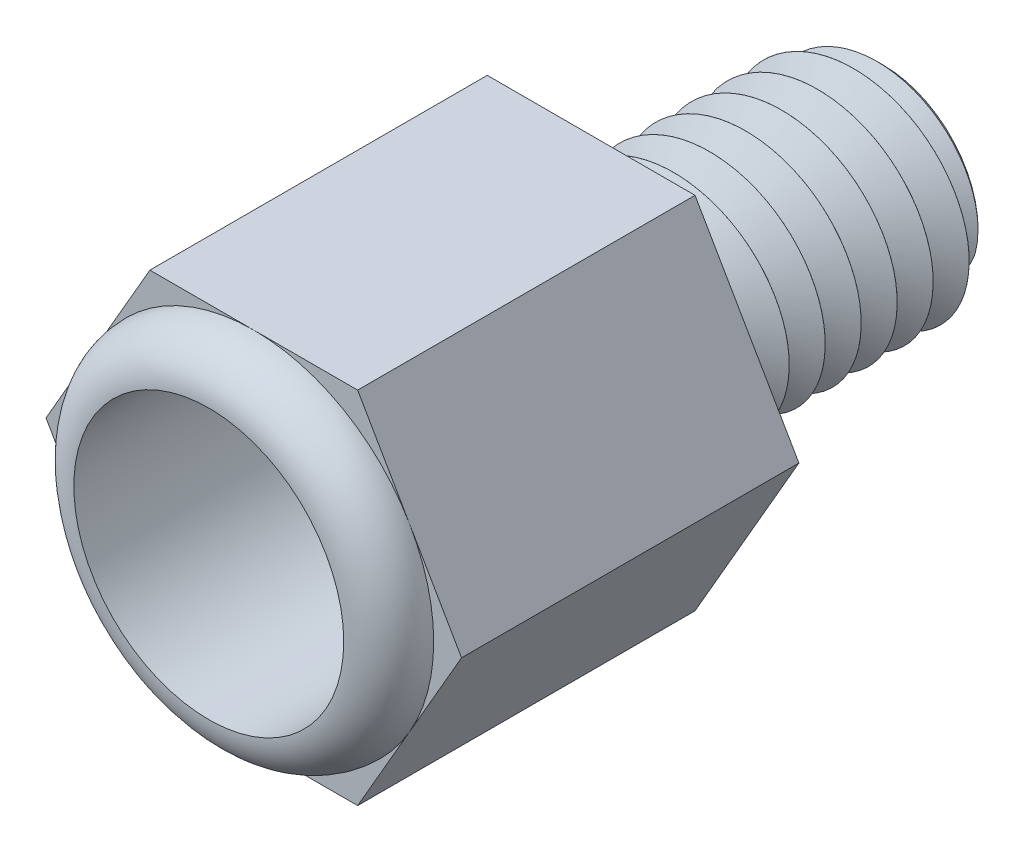
SolidWorks part; units mm, degrees
material "Bronze commercial, UNS C22000 (90-10 Bronze)"
ref_plane "Plan de face" through (0, 0, 0) normal (0, 0, 1) x (1, 0, 0)
ref_plane "Plan de dessus" through (0, 0, 0) normal (0, 1, 0) x (1, 0, 0)
ref_plane "Plan de droite" through (0, 0, 0) normal (1, 0, 0) x (0, 0, -1)
ref_plane "Plan1" through (0, 0, -0.8) normal (0, 0, 1) x (1, 0, 0)
sketch "Esquisse1" plane through (0, 0, 0) normal (0, 0, 1) x (1, 0, 0)
  line L1 (1.7321, 0) -> (0.866, 1.5)
  line L2 (0.866, 1.5) -> (-0.866, 1.5)
  line L3 (-0.866, 1.5) -> (-1.7321, 0)
  line L4 (-1.7321, 0) -> (-0.866, -1.5)
  line L5 (-0.866, -1.5) -> (0.866, -1.5)
  line L6 (0.866, -1.5) -> (1.7321, 0)
  circle A0 centre (0, 0) radius 2.5
  circle A1 centre (0, 0) radius 1.5 construction
  dimension "D1" = 5
  dimension "D2" = 3
extrude "Boss.-Extru.1" add sketch "Esquisse1" along normal blind 6.5
sketch "Forme" plane through (0, 0, 0) normal (1, 0, 0) x (0, 0, -1)
  line L0 (0, -1.808) -> (-0.3995, -2.5)
  line L1 (0, -2.5) -> (0, 2.5) construction
  line L2 (-0.3995, -2.5) -> (0.3995, -2.5)
  line L3 (0.3995, -2.5) -> (0, -1.808)
  line L4 (-6.5, -2.5) -> (0, -2.5) construction
  dimension "D1" = 60
  dimension "D2" = 0.799
sketch "Esquisse3" plane through (0, 0, -0.8) normal (0, 0, -1) x (-1, 0, 0)
  circle A0 centre (0, 0) radius 2.5
  dimension "D1" = 5
curve "Hélice/Spirale1" pitch 0.8 height 7 radius 2.5 centre (0, 0, -0.8) axis (0, 0, 1) start towards (-1, 0, 0)
chamfer "Chanfrein1" distance 0.4 angle 45 1 edges at (2.5, 0, 0)
sweep "Filetage M5" cut profiles "Forme" path "Hélice/Spirale1" align with end faces yes
sketch "Esquisse4" plane through (0, 0, 0) normal (0, 0, -1) x (-1, 0, 0)
  circle A0 centre (0, 0) radius 1.8
  dimension "D1" = 3.6
extrude "Enlèv. mat.-Extru.1" cut sketch "Esquisse4" against normal blind 2.3
sketch "Esquisse5" plane through (0, 0, 6.5) normal (0, 0, 1) x (1, 0, 0)
  line L1 (4.6188, 0) -> (2.3094, 4)
  line L2 (2.3094, 4) -> (-2.3094, 4)
  line L3 (-2.3094, 4) -> (-4.6188, 0)
  line L4 (-4.6188, 0) -> (-2.3094, -4)
  line L5 (-2.3094, -4) -> (2.3094, -4)
  line L6 (2.3094, -4) -> (4.6188, 0)
  circle A0 centre (0, 0) radius 4 construction
  circle A1 centre (0, 0) radius 1.7821
  dimension "D1" = 8
  dimension "D2" = 3.5641
extrude "Boss.-Extru.2" add sketch "Esquisse5" along normal blind 7.5
sketch "Esquisse6" plane through (0, 0, 14) normal (0, 0, 1) x (1, 0, 0)
  circle A0 centre (0, 0) radius 1.7821
  circle A1 centre (0, 0) radius 4
  dimension "D1" = 3.5641
  dimension "D2" = 8
extrude "Boss.-Extru.3" add sketch "Esquisse6" along normal blind 1
fillet "Congé1" radius 1 1 edges at (4, 0, 15)
sketch "Esquisse7" plane through (0, 0, 15) normal (0, 0, 1) x (1, 0, 0)
  circle A0 centre (0, 0) radius 3
  dimension "D1" = 6
extrude "Enlèv. mat.-Extru.2" cut sketch "Esquisse7" against normal blind 5
